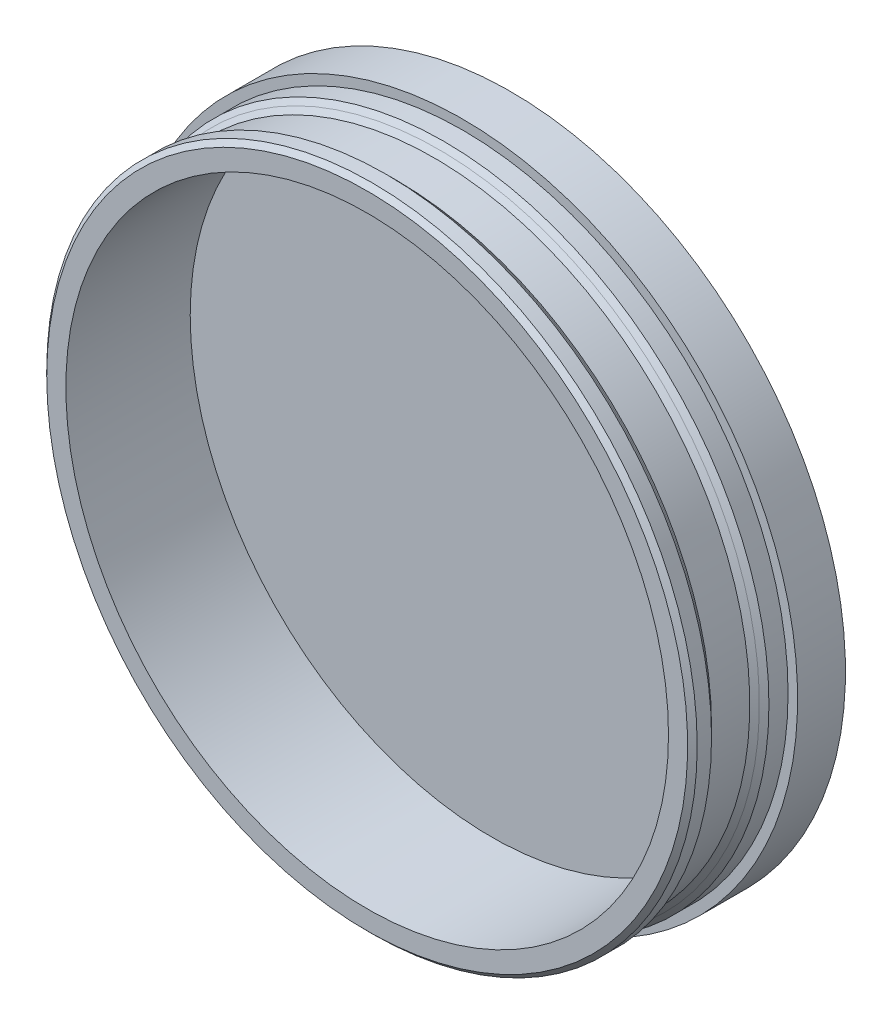
SolidWorks part; units mm, degrees
ref_plane "Front Plane" through (0, 0, 0) normal (0, 0, 1) x (1, 0, 0)
ref_plane "Top Plane" through (0, 0, 0) normal (0, 1, 0) x (1, 0, 0)
ref_plane "Right Plane" through (0, 0, 0) normal (1, 0, 0) x (0, 0, -1)
sketch "Sketch1" plane through (0, 0, 0) normal (0, 1, 0) x (1, 0, 0)
  line L0 (0, 99.2979) -> (0, -58.5521) construction
  line L1 (-100.4208, 0) -> (85.3417, 0) construction
  line L2 (25.025, 0) -> (25.025, 20)
  line L3 (25.025, 20) -> (28.025, 20)
  line L4 (28.025, 20) -> (28.025, 15)
  line L5 (28.025, 15) -> (35, 15)
  line L6 (35, 15) -> (35, 10)
  line L7 (35, 10) -> (34, 10)
  line L9 (34, 2.5) -> (33, 2.5)
  line L10 (33, 2.5) -> (33, 7.5)
  line L11 (33, 7.5) -> (34, 7.5)
  line L13 (34, 0) -> (25.025, 0)
  line L14 (34, 10) -> (34, 7.5)
  line L15 (34, 2.5) -> (34, 0)
  dimension "D1" = 25.025
  dimension "D2" = 3
  dimension "D3" = 35
  dimension "D4" = 34
  dimension "D5" = 34
  dimension "D6" = 5
  dimension "D7" = 5
  dimension "D8" = 20
  dimension "D9" = 5
  dimension "D10" = 2.5
  dimension "D11" = 1
revolve "Revolve1" add sketch "Sketch1" angle 360 about L0
chamfer "Chamfer1" distance 0.5 angle 45 2 edges at (-28.025, 0, -20) (-25.025, 0, -20)
chamfer "Chamfer2" distance 0.5 angle 45 5 edges at (-34, 0, -2.5) (-33, 0, -2.5) (-33, 0, -7.5) (-34, 0, -7.5) (-34, 0, 0)
sketch "Sketch3" plane through (0, 0, -15) normal (0, 0, -1) x (-1, 0, 0)
  circle A0 centre (0, 0) radius 28.025
  dimension "D1" = 56.05
extrude "Boss-Extrude1" add sketch "Sketch3" against normal blind 2
sketch "Sketch4" plane through (0, 0, 0) normal (0, 1, 0) x (1, 0, 0)
  line L0 (35, 15) -> (-35, 15) construction
  line L1 (-35, 15) -> (36.1556, 15)
  line L2 (-35, 15) -> (-35, 25.3399)
  line L3 (-35, 25.3399) -> (36.1556, 25.3399)
  line L4 (36.1556, 15) -> (36.1556, 25.3399)
extrude "Cut-Extrude1" cut sketch "Sketch4" against normal through all both and the other way through all
sketch "Sketch5" plane through (0, 0, 0) normal (0, 0, 1) x (1, 0, 0)
  circle A0 centre (0, 0) radius 31.5
  dimension "D1" = 63
extrude "Cut-Extrude2" cut sketch "Sketch5" against normal up to surface (13 mm away) up to face at (-25.025, 0, -13)
